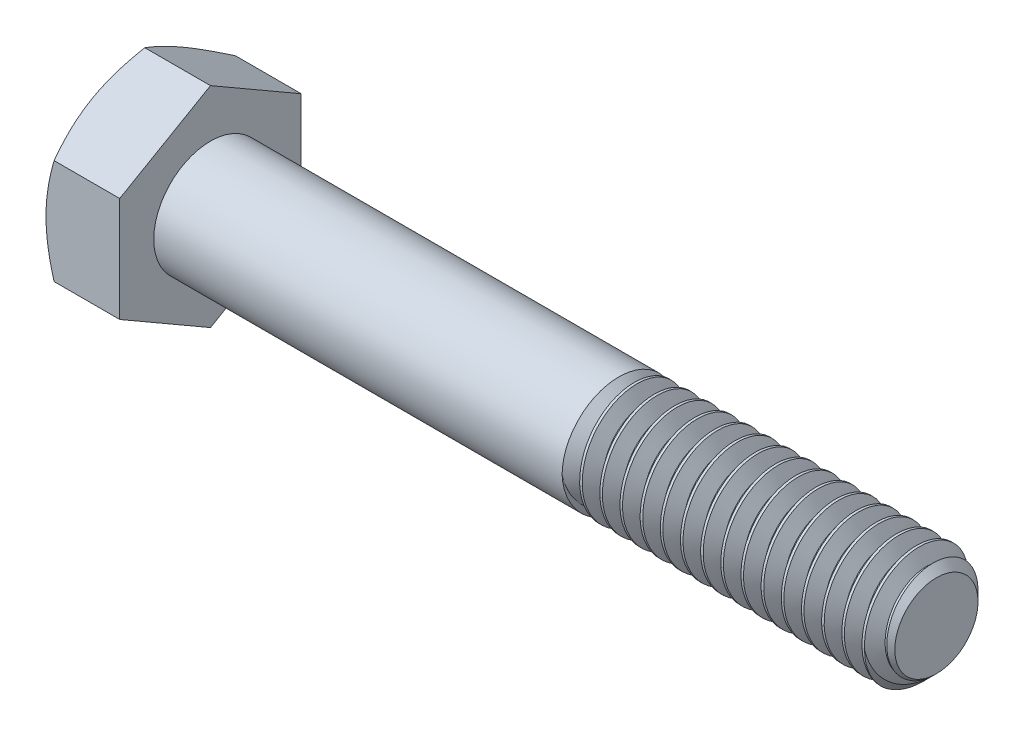
SolidWorks part; units mm, degrees
ref_plane "Front Plane" through (0, 0, 0) normal (0, 0, 1) x (1, 0, 0)
ref_plane "Top Plane" through (0, 0, 0) normal (0, 1, 0) x (1, 0, 0)
ref_plane "Right Plane" through (0, 0, 0) normal (1, 0, 0) x (0, 0, -1)
sketch "Sketch1" plane through (0, 0, 0) normal (0, 0, 1) x (1, 0, 0)
  line L0 (-27.9797, 0) -> (27.9797, 0) construction
  line L1 (27.9797, 3.9688) -> (27.9797, -3.9688) construction
  line L2 (-22.8203, 6.35) -> (-22.8203, -6.35) construction
  line L3 (-27.9797, 6.35) -> (-27.9797, -6.35) construction
  point P9 (-22.8203, 0)
  point P10 (23.0408, -3.9688)
  dimension "Screw Dia" = 7.9375
  dimension "Hex" = 12.7
  dimension "Head Ht" = 5.1594
  dimension "Screw Lenght" = 50.8
  dimension "D1" = 4.9389
ref_plane "Plane2" through (27.9797, 0, 0) normal (1, 0, 0) x (0, 0, -1)
sketch "Sketch5" plane through (27.9797, 0, 0) normal (1, 0, 0) x (0, 0, -1)
  circle A0 centre (0, 0) radius 3.9688
extrude "Boss-Extrude3" add sketch "Sketch5" against normal up to vertex (50.8 mm away) up to point (-22.8203, 0, 0)
sketch "Sketch9" plane through (27.9797, 0, 0) normal (1, 0, 0) x (0, 0, -1)
  circle A1 centre (0, 0) radius 3.9688
  circle A2 centre (0, 0) radius 3.9688
  dimension "D1" = 0
curve "Helix/Spiral1" pitch 1.4111 height 23.6361 turns 16.75 parameters "Pitch"=1.4111
chamfer "Chamfer1" distance 1.0583 angle 45 1 edges at (27.9797, 0, -3.9688)
sketch "Sketch10" plane through (0, 0, 0) normal (0, 0, 1) x (1, 0, 0)
  line L0 (27.9797, 3.9688) -> (28.5089, 3.0522)
  line L1 (28.5089, 3.0522) -> (28.6852, 3.0522)
  line L2 (28.6852, 3.0522) -> (29.2144, 3.9687)
  line L3 (27.9797, 3.9688) -> (29.2144, 3.9687)
  line L4 (28.597, 3.9688) -> (28.597, 3.0522) construction
  line L5 (28.2443, 3.5105) -> (28.9498, 3.5105) construction
  dimension "D1" = 60
  dimension "D2" = 0.1764
  dimension "D3" = 0.7056
sweep "Cut-Sweep1" cut profiles "Sketch10" path "Helix/Spiral1" align with end faces yes
sketch "Sketch11" plane through (0, 0, 0) normal (0, 0, 1) x (1, 0, 0)
  line L0 (-22.8203, 3.9688) -> (-22.8203, 0)
  line L1 (-22.8203, 0) -> (9.7234, 0)
  line L3 (9.7234, 0) -> (5.7547, 3.9688)
  line L4 (-22.8203, 3.9688) -> (5.7547, 3.9688)
  dimension "D1" = 45
  dimension "MIn Thread" = 22.225
revolve "Revolve1" add sketch "Sketch11" angle 360 about L1
sketch "Sketch6" plane through (-22.8203, 0, 0) normal (-1, 0, 0) x (0, 0, 1)
  line L0 (0, 6.35) -> (0, -6.35) construction
  line L1 (6.35, 3.6662) -> (0, 7.3323)
  line L2 (0, 7.3323) -> (-6.35, 3.6662)
  line L3 (-6.35, 3.6662) -> (-6.35, -3.6662)
  line L4 (-6.35, -3.6662) -> (0, -7.3323)
  line L5 (0, -7.3323) -> (6.35, -3.6662)
  line L6 (6.35, -3.6662) -> (6.35, 3.6662)
  circle A0 centre (0, 0) radius 6.35 construction
extrude "Boss-Extrude4" add sketch "Sketch6" along normal up to vertex (5.1594 mm away) up to point (-27.9797, -6.35, 0)
sketch "Sketch7" plane through (-27.9797, 0, 0) normal (-1, 0, 0) x (0, 0, 1)
  circle A0 centre (0, 0) radius 6.35 construction
  circle A1 centre (0, 0) radius 6.35
sketch "Sketch8" plane through (-27.9797, 0, 0) normal (-1, 0, 0) x (0, 0, 1)
  circle A0 centre (0, 0) radius 6.35 construction
  circle A1 centre (0, 0) radius 6.35
extrude "Cut-Extrude3" cut sketch "Sketch8" against normal through all draft 60 flip side to cut
sketch "Sketch12" plane through (-27.9797, 0, 0) normal (-1, 0, 0) x (0, 0, 1)
  line L0 (0, 4.8895) -> (0, 2.7305) construction
  line L1 (0.1905, 4.8895) -> (0.1905, 2.7305)
  line L2 (-0.1905, 4.8895) -> (-0.1905, 2.7305)
  line L3 (0, 3.9688) -> (0, -3.9688) construction
  arc A0 (0.1905, 4.8895) -> (-0.1905, 4.8895) centre (0, 4.8895) ccw
  arc A1 (-0.1905, 2.7305) -> (0.1905, 2.7305) centre (0, 2.7305) ccw
  circle A3 centre (0, 0) radius 2.54 construction
  circle A4 centre (0, 0) radius 5.08 construction
  point P2 (0, 3.81)
  dimension "D1" = 5.08
  dimension "D3" = 10.16
  dimension "D2" = 0.381
extrude "Cut-Extrude4" cut sketch "Sketch12" against normal blind 0.254
pattern_circular "CirPattern1" count 3 over 360 about axis through (0, 0, 0) along (1, 0, 0) of "Cut-Extrude4"
equation "\"D2@Sketch10\" = \"Pitch@Helix/Spiral1\"*.125"
equation "\"D3@Sketch10\" = \"Pitch@Helix/Spiral1\"*.5"
equation "\"D3@Helix/Spiral1\" = \"MIn Thread@Sketch11\"+\"Pitch@Helix/Spiral1\""
equation "\"D1@Chamfer1\" = \"Pitch@Helix/Spiral1\"*.75"
equation "\"D1@Sketch12\" = \"Hex@Sketch1\"*.4"
equation "\"D3@Sketch12\" = \"Hex@Sketch1\"*.8"
equation "\"D2@Sketch12\" = \"Hex@Sketch1\"*.03"
equation "\"D1@Sketch1\" = \"Pitch@Helix/Spiral1\"*3.5"
